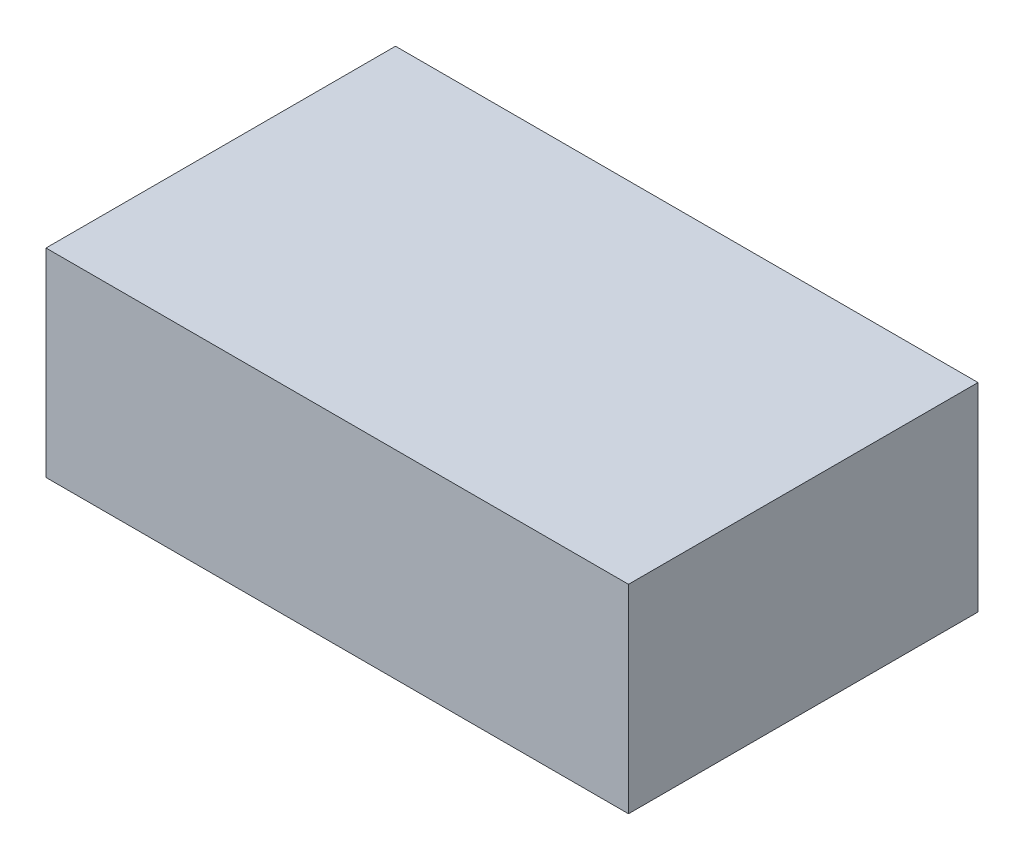
SolidWorks part; units mm, degrees
ref_plane "Front" through (0, 0, 0) normal (0, 0, 1) x (1, 0, 0)
ref_plane "Top" through (0, 0, 0) normal (0, 1, 0) x (1, 0, 0)
ref_plane "Right" through (0, 0, 0) normal (1, 0, 0) x (0, 0, -1)
sketch "Sketch1" plane through (0, 0, 0) normal (0, 1, 0) x (1, 0, 0)
  line L1 (0, 0) -> (38.1, 0)
  line L2 (0, 0) -> (0, 22.86)
  line L3 (0, 22.86) -> (38.1, 22.86)
  line L4 (38.1, 0) -> (38.1, 22.86)
  dimension "D1" = 22.86
  dimension "D2" = 38.1
extrude "Boss-Extrude1" add sketch "Sketch1" along normal blind 13
